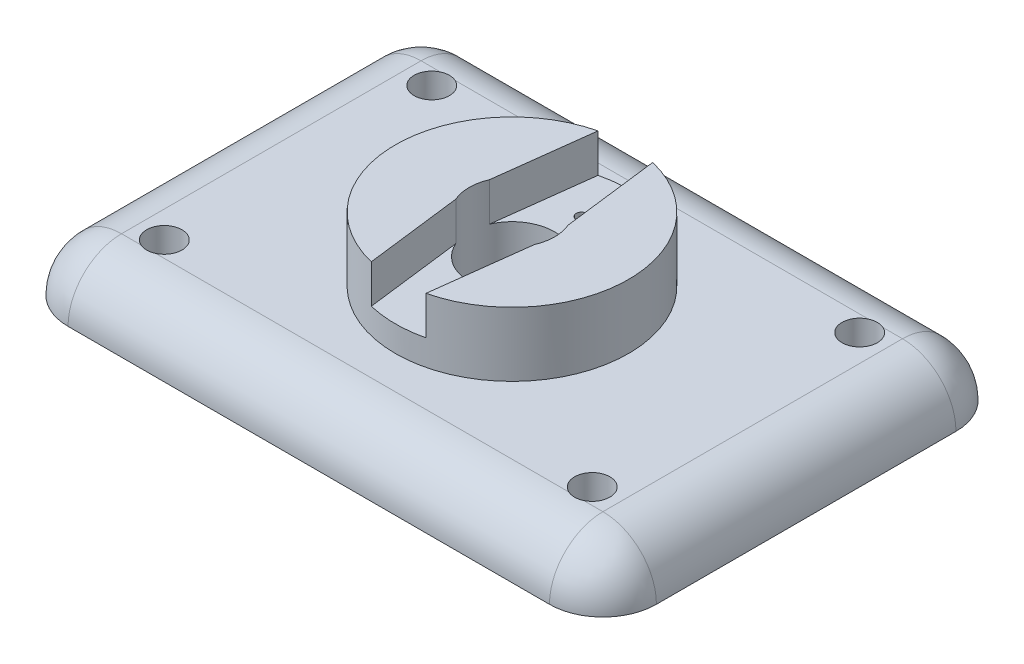
SolidWorks part; units mm, degrees
ref_plane "前视基准面" through (0, 0, 0) normal (0, 0, 1) x (1, 0, 0)
ref_plane "上视基准面" through (0, 0, 0) normal (0, 1, 0) x (1, 0, 0)
ref_plane "右视基准面" through (0, 0, 0) normal (1, 0, 0) x (0, 0, -1)
sketch "草图1" plane through (0, 0, 0) normal (0, 1, 0) x (1, 0, 0)
  line L1 (-27.5, 19) -> (27.5, 19)
  line L2 (-27.5, 19) -> (-27.5, -19)
  line L3 (-27.5, -19) -> (27.5, -19)
  line L4 (27.5, 19) -> (27.5, -19)
  line L5 (-27.5, 19) -> (27.5, -19) construction
  line L6 (-27.5, -19) -> (27.5, 19) construction
  point P0 (0, 0)
  dimension "D1" = 55
  dimension "D2" = 38
extrude "凸台-拉伸1" add sketch "草图1" along normal blind 5
sketch "草图2" plane through (0, 5, 0) normal (0, 1, 0) x (1, 0, 0)
  circle A0 centre (0, 0) radius 10.9
  dimension "D1" = 21.8
extrude "凸台-拉伸2" add sketch "草图2" along normal blind 6
sketch "草图3" plane through (0, 0, 0) normal (0, -1, 0) x (1, 0, 0)
  circle A0 centre (0, 0) radius 4
  dimension "D1" = 8
extrude "切除-拉伸1" cut sketch "草图3" against normal through all
sketch "草图4" plane through (0, 11, 0) normal (0, 1, 0) x (1, 0, 0)
  line L0 (3.6748, -1.5798) -> (2.3413, -12.3203)
  line L1 (0, -1000) -> (0, 49000) construction
  line L2 (-1000, 0) -> (49000, 0) construction
  line L3 (-3.6748, -1.5798) -> (-2.3413, -12.3203)
  line L4 (-3.6748, 1.5798) -> (-2.3413, 12.3203)
  line L5 (3.6748, 1.5798) -> (2.3413, 12.3203)
  line L6 (2.3413, -12.3203) -> (-2.3413, -12.3203)
  line L7 (2.3413, 12.3203) -> (-2.3413, 12.3203)
  line L8 (3.6748, -1.5798) -> (-3.6748, -1.5798)
  line L9 (3.6748, 1.5798) -> (-3.6748, 1.5798)
  circle A1 centre (0, 0) radius 4 construction
extrude "切除-拉伸2" cut sketch "草图4" against normal blind 3.6
sketch "草图5" plane through (0, 7.4, 0) normal (0, 1, 0) x (1, 0, 0)
  line L0 (-6.05, 0) -> (6.05, 0) construction
  circle A0 centre (0, -6.5) radius 0.5
  circle A1 centre (0, 6.5) radius 0.5
  dimension "D1" = 1
  dimension "D3" = 1
  dimension "D2" = 6.5
  dimension "D4" = 6.5
extrude "切除-拉伸3" cut sketch "草图5" against normal blind 4
fillet "圆角1" radius 5 1 edges at (27.5, 2.5, 19) type face fillet first side face at (27.5, 2.5, 0) second side face at (0, 2.5, 19)
fillet "圆角2" radius 5 1 edges at (-27.5, 2.5, 19) type face fillet first side face at (-2.5, 2.5, 19) second side face at (-27.5, 2.5, 0)
fillet "圆角3" radius 5 1 edges at (-27.5, 2.5, -19) type face fillet first side face at (-27.5, 2.5, -2.5) second side face at (0, 2.5, -19)
fillet "圆角4" radius 5 1 edges at (27.5, 2.5, -19) type face fillet first side face at (27.5, 2.5, -2.5) second side face at (2.5, 2.5, -19)
fillet "圆角5" radius 5 1 edges at (27.5, 5, 0) type face fillet first side face at (0, 5, 10.9) second side face at (27.5, 2.5, 0)
sketch "草图6" plane through (0, 0, 0) normal (0, -1, 0) x (1, 0, 0)
  line L1 (-20, -12.5) -> (20, -12.5) construction
  line L2 (-20, -12.5) -> (-20, 12.5) construction
  line L3 (-20, 12.5) -> (20, 12.5) construction
  line L4 (20, -12.5) -> (20, 12.5) construction
  line L5 (-20, -12.5) -> (20, 12.5) construction
  line L6 (-20, 12.5) -> (20, -12.5) construction
  circle A0 centre (-20, 12.5) radius 1.65
  circle A1 centre (20, 12.5) radius 1.65
  circle A2 centre (20, -12.5) radius 1.65
  circle A3 centre (-20, -12.5) radius 1.65
  point P0 (0, 0)
  dimension "D3" = 3.3
  dimension "D1" = 40
  dimension "D2" = 25
extrude "切除-拉伸4" cut sketch "草图6" against normal through all
